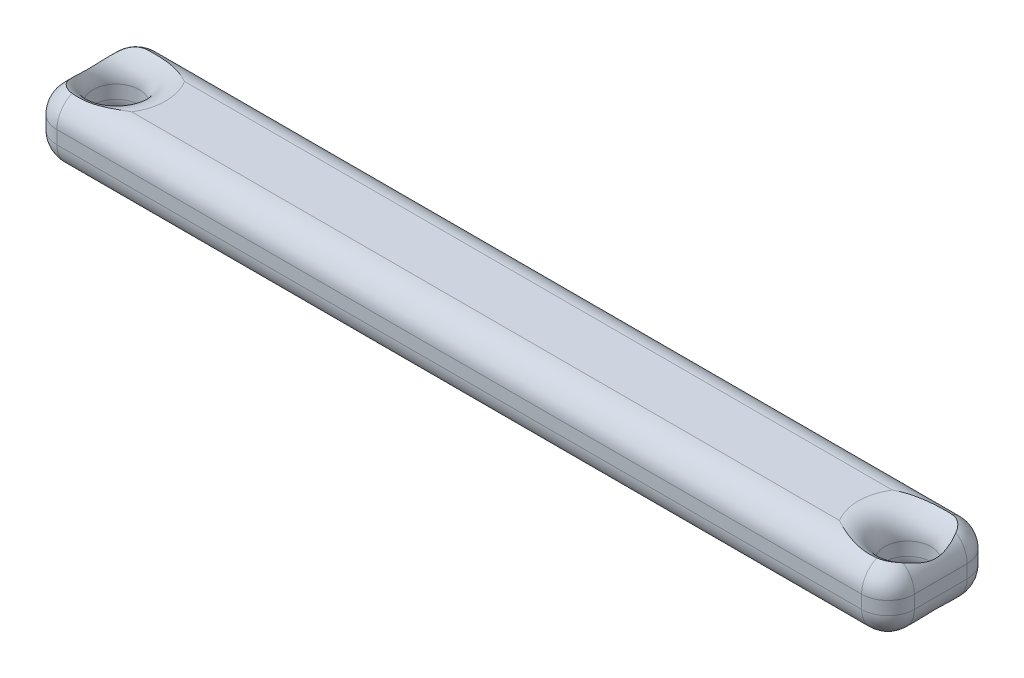
SolidWorks part; units mm, degrees
ref_plane "Front Plane" through (0, 0, 0) normal (0, 0, 1) x (1, 0, 0)
ref_plane "Top Plane" through (0, 0, 0) normal (0, 1, 0) x (1, 0, 0)
ref_plane "Right Plane" through (0, 0, 0) normal (1, 0, 0) x (0, 0, -1)
sketch "Sketch1" plane through (0, 0, 0) normal (0, 0, 1) x (1, 0, 0)
  line L0 (0, 0) -> (-17832.1255, 0) construction
  line L2 (-29.7361, 2.5) -> (35.2639, 2.5)
  line L3 (-29.7361, 2.5) -> (-29.7361, -2.5)
  line L4 (-29.7361, -2.5) -> (35.2639, -2.5)
  line L5 (35.2639, 2.5) -> (35.2639, -2.5)
  dimension "D1" = 65
  dimension "D2" = 2.5
  dimension "D3" = 5
extrude "Boss-Extrude1" add sketch "Sketch1" against normal blind 8
sketch "Sketch2" plane through (0, 2.5, 0) normal (0, 1, 0) x (1, 0, 0)
  line L0 (2.7639, 8) -> (2.7639, -2.5581) construction
  line L1 (35.2639, 8) -> (-29.7361, 8) construction
  line L2 (35.2639, 0) -> (-29.7361, 0) construction
  line L4 (35.2639, 8) -> (35.2639, 0) construction
  circle A0 centre (32.7639, 4) radius 1.75
  circle A1 centre (-27.2361, 4) radius 1.75
  point P8 (0, 0)
  point P9 (0, 0)
  point P10 (35.2639, 3.7151)
  dimension "D1" = 3.5
  dimension "D2" = 4
  dimension "D3" = 2.5
extrude "Cut-Extrude1" cut sketch "Sketch2" against normal through all contours A1 | A0
fillet "Fillet1" radius 2 16 edges at (-25.4861, -2.5, -4) (31.0139, -2.5, -4) (2.7639, -2.5, -8) (35.2639, 0, -8) (35.2639, -2.5, -4) (-29.7361, -2.5, -4) (-29.7361, 0, -8) (35.2639, 0, 0) (2.7639, -2.5, 0) (-29.7361, 0, 0) (-25.4861, 2.5, -4) (31.0139, 2.5, -4) (-29.7361, 2.5, -4) (2.7639, 2.5, -8) (35.2639, 2.5, -4) (2.7639, 2.5, 0)
